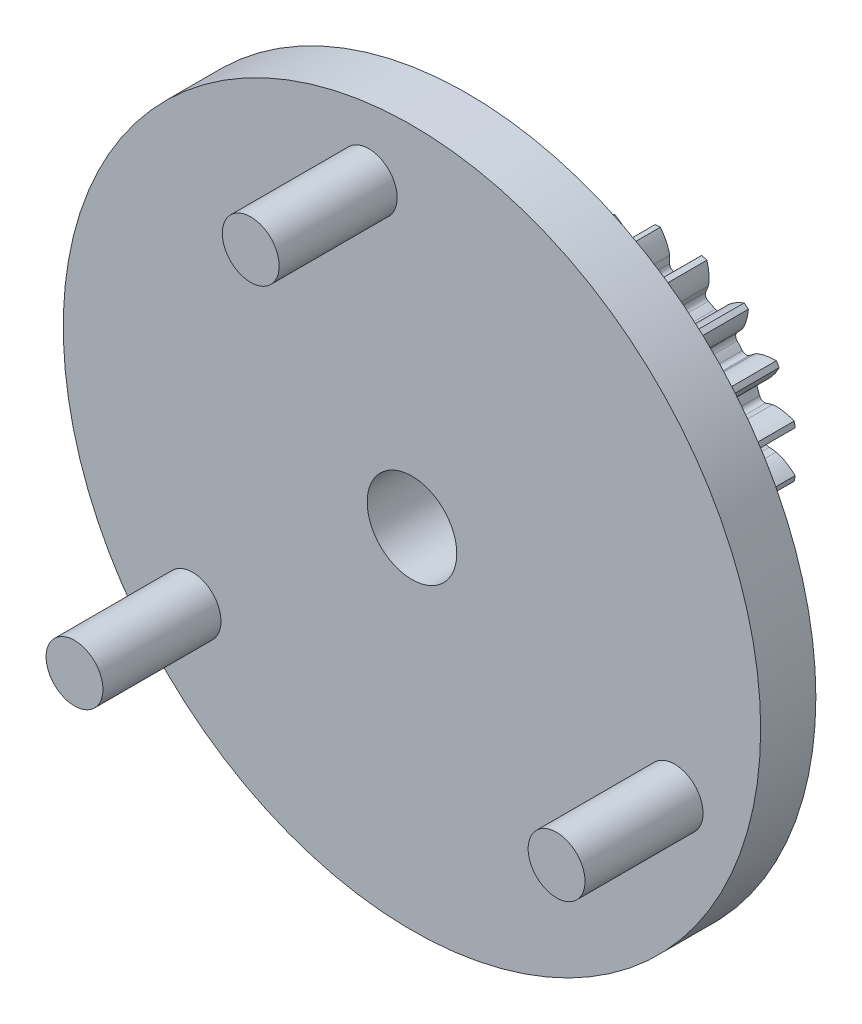
SolidWorks part; units mm, degrees
ref_plane "Front Plane" through (0, 0, 0) normal (0, 0, 1) x (1, 0, 0)
ref_plane "Top Plane" through (0, 0, 0) normal (0, 1, 0) x (1, 0, 0)
ref_plane "Right Plane" through (0, 0, 0) normal (1, 0, 0) x (0, 0, -1)
ref_axis "Gear Axis" through (0, 0, -1.7501) along (0, 0, 1)
sketch "Blank Sketch" plane through (0, 0, 0) normal (0, 0, 1) x (1, 0, 0)
  circle A0 centre (0, 0) radius 11.875
  dimension "OD" = 23.75
extrude "Blank" add sketch "Blank Sketch" along normal blind 5
sketch "Tooth Space Sketch" plane through (0, 0, 0) normal (0, 0, 1) x (1, 0, 0)
  line L0 (9.9424, 0.9134) -> (9.2988, 0.8543)
  line L1 (9.9424, -0.9134) -> (9.2988, -0.8543)
  line L2 (12.7535, 3.1007) -> (12.7535, -3.1007)
  arc A0 (9.2988, 0.8543) -> (8.8676, 0.3619) centre (9.3422, 0.3813) ccw
  arc A1 (8.8676, -0.3619) -> (9.2988, -0.8543) centre (9.3422, -0.3813) ccw
  arc A2 (8.8676, -0.3619) -> (8.8676, 0.3619) centre (0, 0) ccw
  spline S0 degree 4 poles (9.9424, 0.9134) (9.9477, 0.914) (9.9627, 0.9159) (9.9908, 0.9208) (10.0364, 0.9304) (10.094, 0.9451) (10.1679, 0.9668) (10.254, 0.9959) (10.3477, 1.0316) (10.4483, 1.0743) (10.5475, 1.1204) (10.6453, 1.1696) (10.7417, 1.2214) (10.857, 1.2875) (10.9932, 1.3713) (11.1493, 1.4758) (11.3226, 1.602) (11.4947, 1.7386) (11.6604, 1.8795) (11.8233, 2.0291) (11.9776, 2.179) (12.1329, 2.3418) (12.2737, 2.4958) (12.4257, 2.676) (12.5467, 2.8236) (12.6999, 3.0262) (12.7884, 3.1482) (12.8897, 3.2936) (12.9335, 3.3596) (12.9605, 3.4002) knots 0 0 0 0 0 0.005377 0.015084 0.028532 0.04661 0.064855 0.092111 0.119476 0.146842 0.174209 0.201575 0.228941 0.256307 0.307035 0.361767 0.4165 0.471232 0.525964 0.580697 0.635429 0.690161 0.744894 0.799626 0.854358 0.909091 0.954545 1 1 1 1 1 construction
  spline S1 degree 4 poles (9.9424, 0.9134) (9.9477, 0.914) (9.9627, 0.9159) (9.9908, 0.9208) (10.0364, 0.9304) (10.094, 0.9451) (10.1679, 0.9668) (10.254, 0.9959) (10.3477, 1.0316) (10.4483, 1.0743) (10.5475, 1.1204) (10.6453, 1.1696) (10.7417, 1.2214) (10.857, 1.2875) (10.9932, 1.3713) (11.1493, 1.4758) (11.3226, 1.602) (11.4947, 1.7386) (11.6604, 1.8795) (11.8233, 2.0291) (11.9776, 2.179) (12.1329, 2.3418) (12.2737, 2.4958) (12.4257, 2.676) (12.5467, 2.8236) (12.6667, 2.9823) (12.7243, 3.0604) (12.7535, 3.1007) knots 0 0 0 0 0 0.005377 0.015084 0.028532 0.04661 0.064855 0.092111 0.119476 0.146842 0.174209 0.201575 0.228941 0.256307 0.307035 0.361767 0.4165 0.471232 0.525964 0.580697 0.635429 0.690161 0.744894 0.799626 0.854358 0.909091 0.909091 0.909091 0.909091 0.909091
  spline S2 degree 4 poles (9.9424, -0.9134) (9.9477, -0.914) (9.9627, -0.9159) (9.9908, -0.9208) (10.0364, -0.9304) (10.094, -0.9451) (10.1679, -0.9668) (10.254, -0.9959) (10.3477, -1.0316) (10.4483, -1.0743) (10.5475, -1.1204) (10.6453, -1.1696) (10.7417, -1.2214) (10.857, -1.2875) (10.9932, -1.3713) (11.1493, -1.4758) (11.3226, -1.602) (11.4947, -1.7386) (11.6604, -1.8795) (11.8233, -2.0291) (11.9776, -2.179) (12.1329, -2.3418) (12.2737, -2.4958) (12.4257, -2.676) (12.5467, -2.8236) (12.6999, -3.0262) (12.7884, -3.1482) (12.8897, -3.2936) (12.9335, -3.3596) (12.9605, -3.4002) knots 0 0 0 0 0 0.005377 0.015084 0.028532 0.04661 0.064855 0.092111 0.119476 0.146842 0.174209 0.201575 0.228941 0.256307 0.307035 0.361767 0.4165 0.471232 0.525964 0.580697 0.635429 0.690161 0.744894 0.799626 0.854358 0.909091 0.954545 1 1 1 1 1 construction
  spline S3 degree 4 poles (9.9424, -0.9134) (9.9477, -0.914) (9.9627, -0.9159) (9.9908, -0.9208) (10.0364, -0.9304) (10.094, -0.9451) (10.1679, -0.9668) (10.254, -0.9959) (10.3477, -1.0316) (10.4483, -1.0743) (10.5475, -1.1204) (10.6453, -1.1696) (10.7417, -1.2214) (10.857, -1.2875) (10.9932, -1.3713) (11.1493, -1.4758) (11.3226, -1.602) (11.4947, -1.7386) (11.6604, -1.8795) (11.8233, -2.0291) (11.9776, -2.179) (12.1329, -2.3418) (12.2737, -2.4958) (12.4257, -2.676) (12.5467, -2.8236) (12.6667, -2.9823) (12.7243, -3.0604) (12.7535, -3.1007) knots 0 0 0 0 0 0.005377 0.015084 0.028532 0.04661 0.064855 0.092111 0.119476 0.146842 0.174209 0.201575 0.228941 0.256307 0.307035 0.361767 0.4165 0.471232 0.525964 0.580697 0.635429 0.690161 0.744894 0.799626 0.854358 0.909091 0.909091 0.909091 0.909091 0.909091
  dimension "Root" = 8.875
  dimension "Fillet" = 0.475
extrude "Tooth Space" cut sketch "Tooth Space Sketch" against normal through all both and the other way through all both
pattern_circular "Teeth" count 17 over 360 about axis through (0, 0, -1.7501) along (0, 0, 1) of "Tooth Space"
sketch "Bore Sketch" plane through (0, 0, 0) normal (0, 0, 1) x (1, 0, 0)
  circle A0 centre (0, 0) radius 4.175
  dimension "Bore" = 8.35
extrude "Bore" cut sketch "Bore Sketch" against normal through all both and the other way through all both
ref_plane "Plane1" through (0, 0, 24) normal (0, 0, 1) x (1, 0, 0)
sketch "Sketch1" plane through (0, 0, 24) normal (0, 0, 1) x (1, 0, 0)
  line L0 (0, 0) -> (-4.0265, 25.9393) construction
  line L1 (0, 0) -> (0, 26.25) construction
  circle A0 centre (0, 0) radius 26.25 construction
  circle A5 centre (-4.0265, 25.9393) radius 2.65
  circle A6 centre (0, 0) radius 4.175
  circle A7 centre (0, 0) radius 32.5
  point P15 (0, 0)
  dimension "D1" = 52.5
  dimension "D3" = 5.3
  dimension "D4" = 8.35
  dimension "D5" = 65
  dimension "D2" = 8.824
extrude "Boss-Extrude1" add sketch "Sketch1" against normal blind 5 separate body contours A7 A5 A6 | A5 region at (-4.0265, 25.9393, 24) region at (-31.5808, 0, 24)
sketch "Sketch3" plane through (0, 0, 19) normal (0, 0, -1) x (-1, 0, 0)
  circle A1 centre (0, 0) radius 4.175
  circle A2 centre (0, 0) radius 8.75
  circle A3 centre (0, 0) radius 4.175 construction
  dimension "D1" = 17.5
extrude "Boss-Extrude2" add sketch "Sketch3" along normal up to surface (14 mm away) up to face at (4.175, 0, 5)
chamfer "Chamfer2" distance 24 angle 30 1 edges at (-8.75, 0, 19) first distance on face at (-8.75, 0, 19)
extrude "Boss-Extrude3" add sketch "Sketch1<5>" along normal blind 11 contours A5
sketch "Sketch1<5>" plane through (0, 0, 24) normal (0, 0, 1) x (1, 0, 0) same geometry as "Sketch1"
pattern_circular "CirPattern1" count 3 over 360 about axis through (0, 0, 19) along (0, 0, 1) of "Boss-Extrude3"
equation "\"No. of Teeth\"= 17"
equation "\"Module\"= 1.25"
equation "\"Bore Diameter\"= 8.35"
equation "\"Pressure Angle\"= 20"
equation "\"Outer Diameter\"= ( \"No. of Teeth\" + 2 ) * \"Module\""
equation "\"Pitch Diameter\"= \"No. of Teeth\" * \"Module\""
equation "\"Backlash\"= IIF ( \"Module\" <= 1 , 0.3 * \"Module\" , 0.3 )"
equation "\"Arc Length\"= ( ( \"Module\" * pi ) / 2 + \"Backlash\" )"
equation "\"Fillet Radius\"= 0.38 * \"Module\""
equation "\"Tooth Depth\"= IIF ( \"Module\" <= 1.25 , \"Module\" * 2.4 , \"Module\" * 2.25 )"
equation "\"Face Width\"= 5"
equation "\"Root Diameter\"= \"Outer Diameter\" - 2 * \"Tooth Depth\""
equation "\"Base Diameter\"= \"Pitch Diameter\" * cos ( \"Pressure Angle\" )"
equation "\"Base Radius\"= \"Base Diameter\" / 2"
equation "\"Tooth Thickness\"= \"Module\" * pi - \"Arc Length\""
equation "\"Half Space Angle\"= ( \"Arc Length\" / \"Pitch Diameter\" ) * 180 / pi"
equation "\"Involute Fn\"= tan ( \"Pressure Angle\" ) - \"Pressure Angle\" * pi / 180"
equation "\"Flank Offset\"= \"Arc Length\" / \"Pitch Diameter\" - \"Involute Fn\""
equation "\"Tip Cap Diameter\"= \"Outer Diameter\" + 2 * \"Module\""
equation "\"Flank Start Diameter\"= IIF ( \"Base Diameter\" >= ( \"Root Diameter\" + 3 * \"Fillet Radius\" ) , \"Base Diameter\" , \"Root Diameter\" + 3 * \"Fillet Radius\" )"
equation "\"Involute t1\"= ( abs ( ( \"Flank Start Diameter\" / \"Base Diameter\" ) ^ 2 - 1 ) ) ^ 0.5"
equation "\"Involute t2\"= ( abs ( ( \"Tip Cap Diameter\" / \"Base Diameter\" ) ^ 2 - 1 ) ) ^ 0.5"
equation "\"Flank Arc Radius\"= ( \"Pitch Diameter\" / 2 ) * sin ( \"Pressure Angle\" )"
equation "\"Flank Centre Angle\"= \"Half Space Angle\" + \"Pressure Angle\""
equation "\"OD@Blank Sketch\"= \"Outer Diameter\""
equation "\"Width@Blank\"= \"Face Width\""
equation "\"Root@Tooth Space Sketch\"= \"Root Diameter\" / 2"
equation "\"Fillet@Tooth Space Sketch\"= \"Fillet Radius\""
equation "\"Count@Teeth\"= \"No. of Teeth\""
equation "\"Bore@Bore Sketch\"= \"Bore Diameter\""
